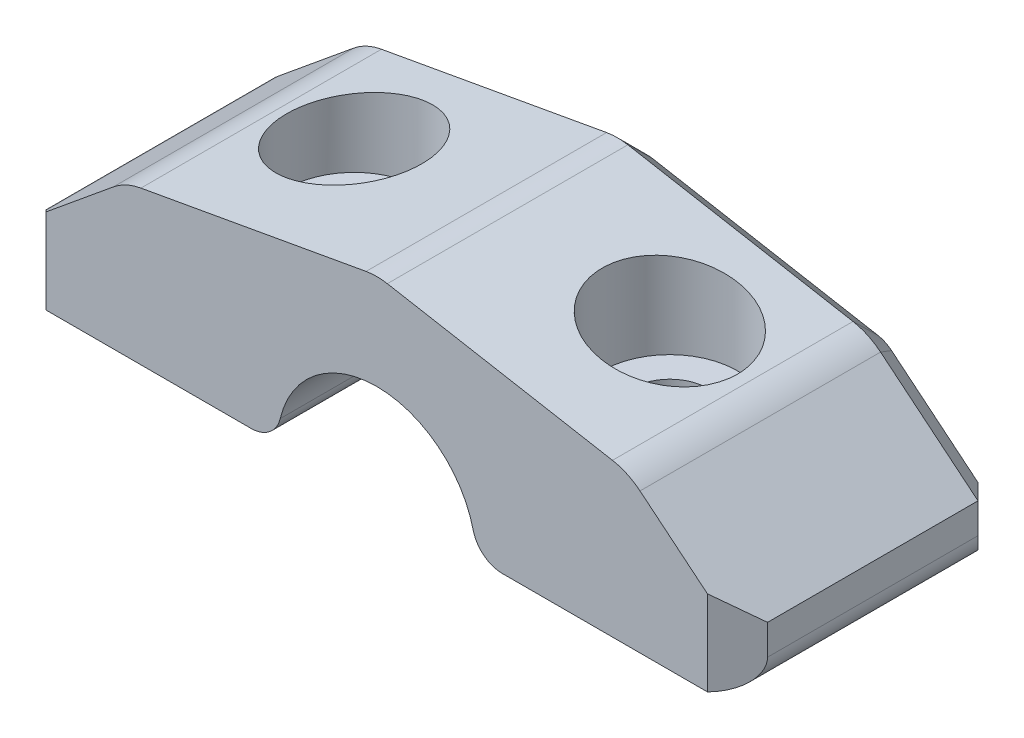
SolidWorks part; units mm, degrees
ref_plane "Front Plane" through (0, 0, 0) normal (0, 0, 1) x (1, 0, 0)
ref_plane "Top Plane" through (0, 0, 0) normal (0, 1, 0) x (1, 0, 0)
ref_plane "Right Plane" through (0, 0, 0) normal (1, 0, 0) x (0, 0, -1)
sketch "Sketch1" plane through (0, 0, 0) normal (0, 0, 1) x (1, 0, 0)
  line L0 (-3.3, 0) -> (-12, 0)
  line L1 (-12, 0) -> (-12, 6.5)
  line L2 (-12, 6.5) -> (12, 6.5)
  line L3 (0, 6.5) -> (0, 3.3) construction
  line L4 (12, 0) -> (12, 6.5)
  line L5 (3.3, 0) -> (12, 0)
  arc A0 (3.3, 0) -> (-3.3, 0) centre (0, 0) ccw
  dimension "D1" = 6.6
  dimension "D2" = 24
  dimension "D3" = 6.5
extrude "Boss-Extrude1" add sketch "Sketch1" along normal blind 9
sketch "Sketch2" plane through (0, 0, 9) normal (0, 0, 1) x (1, 0, 0)
  line L0 (0, 6.5) -> (-8.3557, 5)
  line L1 (12, 6.5) -> (-12, 6.5) construction
  line L2 (-8.3557, 5) -> (-12, 2.0044)
  line L3 (-12, 6.5) -> (-12, 0) construction
  line L4 (-12, 2.0044) -> (-12, 6.5)
  line L5 (-12, 6.5) -> (12, 6.5)
  line L6 (0, 8.1862) -> (0, -3.9101) construction
  line L7 (12, 2.0044) -> (12, 6.5)
  line L8 (8.3557, 5) -> (12, 2.0044)
  line L9 (0, 6.5) -> (8.3557, 5)
  line L10 (-12, 0) -> (-3.3, 0) construction
  line M8 (12, 0) -> (12, 6.5)
  line M9 (12, 6.5) -> (-12, 6.5)
  line M10 (-12, 6.5) -> (-12, 0)
  dimension "D1" = 5
  dimension "D2" = 16.7114
  dimension "D3" = 4.4956
extrude "Cut-Extrude1" cut sketch "Sketch2" against normal through all both and the other way through all contours L2 L0 M9 M10 | L9 L8 M9 M8 region at (-8.6912, 5.286, 9) region at (8.6912, 5.286, 9)
chamfer "Chamfer1" distance 1 angle 45 4 edges at (-12, 1.0022, 0) (12, 1.0022, 0) (12, 1.0022, 9) (-12, 1.0022, 9)
fillet "Fillet3" radius 1 4 edges at (12, 0, 4.5) (3.3, 0, 4.5) (-12, 0, 4.5) (-3.3, 0, 4.5)
sketch "Sketch4" plane through (0, 0, 0) normal (0, -1, 0) x (1, 0, 0)
  line L0 (0, 9) -> (0, 0) construction
  line L1 (-5.25, 4.5) -> (5.25, 4.5) construction
  line L2 (3.2095, 9) -> (-3.2095, 9) construction
  line L4 (-3.2095, 0) -> (3.2095, 0) construction
  circle A0 centre (-5.25, 4.5) radius 1.25
  circle A1 centre (5.25, 4.5) radius 1.25
  point P8 (0, 4.5)
  point P11 (0, 8)
  point P14 (0, 0)
  point P17 (0, 4.5)
  dimension "D2" = 2.5
  dimension "D1" = 10.5
extrude "Cut-Extrude2" cut sketch "Sketch4" against normal through all
sketch "Sketch5" plane through (0, 0, 0) normal (0, 1, 0) x (1, 0, 0)
  circle A0 centre (-5.25, -4.5) radius 2.25
  circle A1 centre (5.25, -4.5) radius 2.25
  dimension "D1" = 4.5
extrude "Cut-Extrude3" cut sketch "Sketch5" along normal blind 10 from offset 3
fillet "Fillet2" radius 2 4 edges at (8.3557, 5, 4.5) (-8.3557, 5, 4.5) (-12, 2.0044, 4.5)
chamfer "Chamfer2" distance 1 angle 45 12 edges at (-9.8794, 3.7476, 0) (-8.3276, 4.9392, 0) (-4.0978, 5.7644, 0) (9.8794, 3.7476, 0) (0, 6.468, 0) (8.3276, 4.9392, 0) (4.0978, 5.7644, 0) (0, 3.3, 0) (-7.5911, 0, 0) (7.5911, 0, 0) (-3.5627, 0.215, 0) (3.5627, 0.215, 0)
